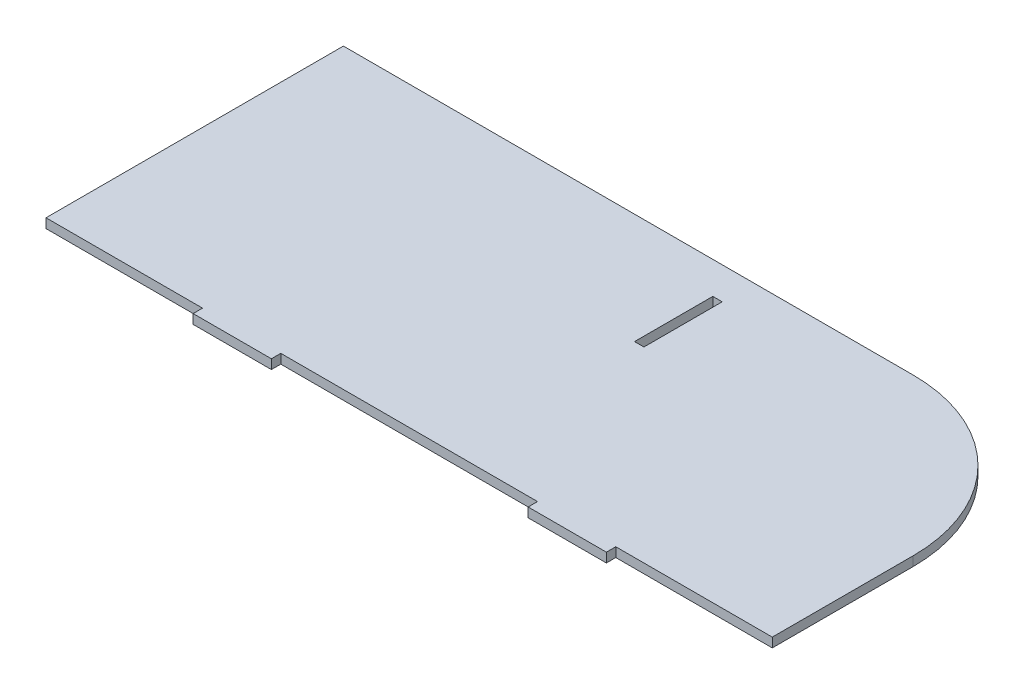
SolidWorks part; units mm, degrees
material "Maple"
ref_plane "Front Plane" through (0, 0, 0) normal (0, 0, 1) x (1, 0, 0)
ref_plane "Top Plane" through (0, 0, 0) normal (0, 1, 0) x (1, 0, 0)
ref_plane "Right Plane" through (0, 0, 0) normal (1, 0, 0) x (0, 0, -1)
sketch "Sketch1" plane through (0, 0, 0) normal (0, 1, 0) x (1, 0, 0)
  line L1 (-232, -63.9598) -> (132, -63.9598)
  line L2 (-232, -63.9598) -> (-232, -253.9598)
  line L3 (-232, -253.9598) -> (-132, -253.9598)
  line L4 (232, -163.9598) -> (232, -253.9598)
  line L13 (-289.5, 225) -> (-289.5, -457) construction
  line L14 (24.5, -84.4598) -> (30.5, -84.4598)
  line L15 (24.5, -84.4598) -> (24.5, -134.4598)
  line L16 (24.5, -134.4598) -> (30.5, -134.4598)
  line L17 (30.5, -84.4598) -> (30.5, -134.4598)
  line L19 (132.0246, -259.9597) -> (82.0246, -259.9598)
  line L21 (-132, -253.9598) -> (-132, -259.9598)
  line L22 (-132, -259.9598) -> (-82, -259.9598)
  line L23 (-82, -253.9598) -> (-82, -259.9598)
  line L24 (132, -253.9598) -> (232, -253.9598)
  line L26 (82.0246, -253.9598) -> (82.0246, -259.9598)
  line L28 (132, -253.9598) -> (132.0246, -259.9597)
  line L29 (-82, -253.9598) -> (82.0246, -253.9598)
  arc A0 (232, -163.9598) -> (132, -63.9598) centre (132, -163.9598) ccw
  point P0 (0, 0)
  dimension "D3" = 100
  dimension "D2" = 190
  dimension "D4" = 50
  dimension "D5" = 190
  dimension "D6" = 50
  dimension "D7" = 20.5
  dimension "D8" = 119.5
  dimension "D9" = 57.5
  dimension "D10" = 100
  dimension "D11" = 100
  dimension "D12" = 50
  dimension "D13" = 190
  dimension "D14" = 6
  dimension "D15" = 6
  dimension "D16" = 6
  dimension "D17" = 6
extrude "Boss-Extrude1" add sketch "Sketch1" along normal blind 6
